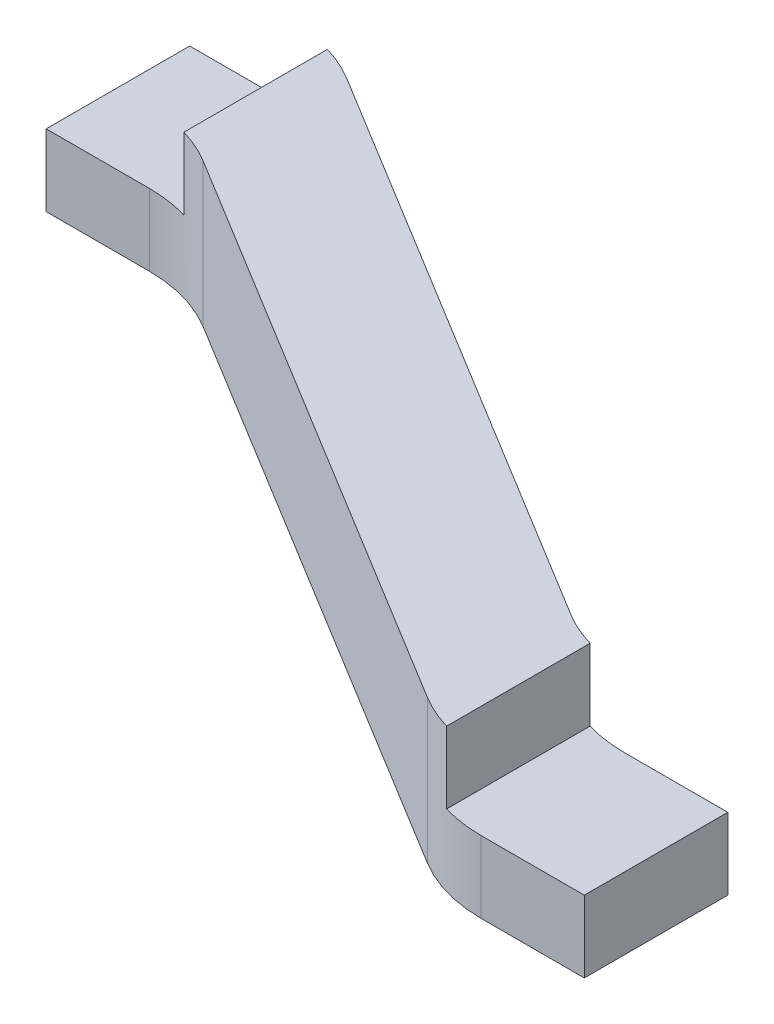
SolidWorks part; units mm, degrees
ref_plane "Alzado" through (0, 0, 0) normal (0, 0, 1) x (1, 0, 0)
ref_plane "Planta" through (0, 0, 0) normal (0, 1, 0) x (1, 0, 0)
ref_plane "Vista lateral" through (0, 0, 0) normal (1, 0, 0) x (0, 0, -1)
sketch "Croquis1" plane through (0, 0, 0) normal (0, 1, 0) x (1, 0, 0)
  line L0 (-65, 0) -> (65, 0) construction
  line L1 (-65, 0) -> (-45, 0)
  line L2 (-45, 0) -> (45, -55)
  line L3 (45, -55) -> (65, -55)
  line L4 (65, -55) -> (65, -75)
  line L5 (65, -75) -> (45, -75)
  line L6 (45, -75) -> (-45, -20)
  line L7 (-45, -20) -> (-65, -20)
  line L8 (-65, -20) -> (-65, 0)
  point P0 (-65, -10)
  point P4 (0, 0)
  point P13 (65, -65)
  dimension "D1" = 130
  dimension "D2" = 20
  dimension "D3" = 20
  dimension "D4" = 55
extrude "Saliente-Extruir1" add sketch "Croquis1" along normal blind 20
fillet "Redondeo1" radius 20 4 edges at (45, 10, 75) (45, 10, 55) (-45, 10, 0) (-45, 10, 20)
sketch "Croquis3" plane through (0, 20, 0) normal (0, 1, 0) x (1, 0, 0)
  line L0 (-65, 0) -> (-45, 0)
  line L1 (-45, 0) -> (-45, -22.7369)
  line L2 (-45, -22.7369) -> (-65, -22.7369)
  line L3 (-65, -22.7369) -> (-65, 0)
  line L4 (-50.6273, 0) -> (-65, 0) construction
  line L5 (65, -52.5479) -> (45, -52.5479)
  line L6 (45, -52.5479) -> (45, -75)
  line L7 (45, -75) -> (65, -75)
  line L8 (65, -75) -> (65, -52.5479)
  line L9 (50.6273, -75) -> (65, -75) construction
  dimension "D1" = 20
  dimension "D2" = 20
extrude "Cortar-Extruir2" cut sketch "Croquis3" against normal blind 10
